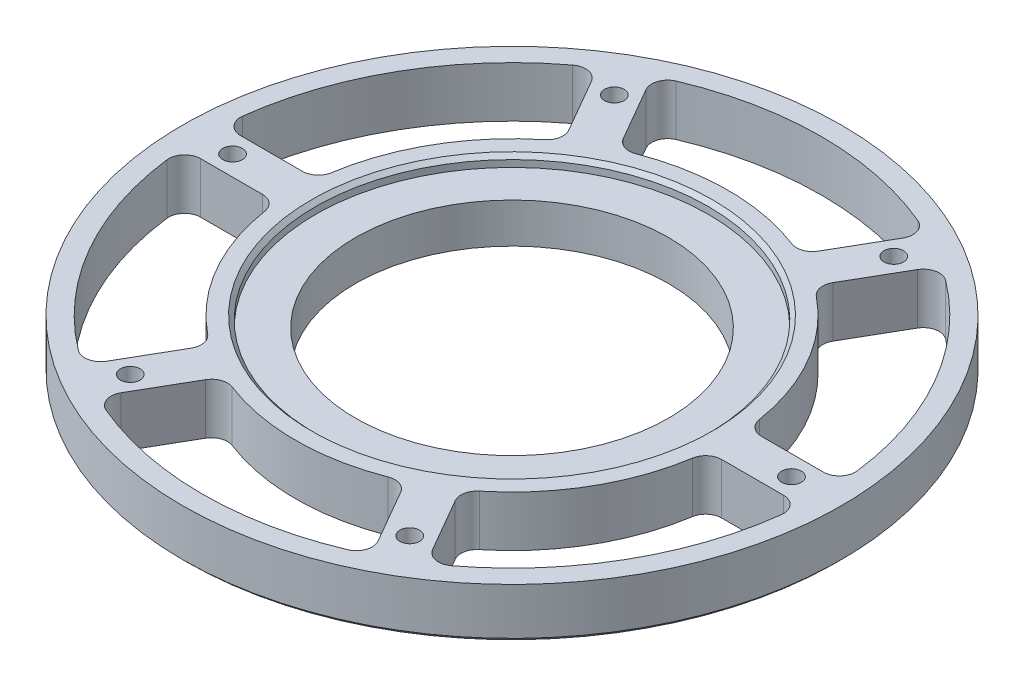
SolidWorks part; units mm, degrees
material "6061-T6 (SS)"
ref_plane "Front Plane" through (0, 0, 0) normal (0, 0, 1) x (1, 0, 0)
ref_plane "Top Plane" through (0, 0, 0) normal (0, 1, 0) x (1, 0, 0)
ref_plane "Right Plane" through (0, 0, 0) normal (1, 0, 0) x (0, 0, -1)
sketch "Sketch2" plane through (0, 0, 0) normal (1, 0, 0) x (0, 0, -1)
  line L0 (-39.2125, 0) -> (-82.55, 0)
  line L1 (-82.55, 0) -> (-82.55, 12.7)
  line L2 (-82.55, 12.7) -> (-49.2125, 12.7)
  line L3 (-49.2125, 12.7) -> (-49.2125, 10)
  line L4 (-49.2125, 10) -> (-39.2125, 10)
  line L5 (-39.2125, 10) -> (-39.2125, 0)
  dimension "D1" = 82.55
  dimension "D2" = 12.7
  dimension "D4" = 49.2125
  dimension "D5" = 10
  dimension "D3" = 10
ref_axis "Axis1" through (0, -0.635, 0) along (0, 1, 0)
revolve "Revolve1" add sketch "Sketch2" angle 360 about axis through (0, -0.635, 0) along (0, 1, 0)
hole_wizard "#10 (0.1935) Diameter Hole1" positions "Sketch6" profile "Sketch7" hole size "#10" standard "ANSI Inch" end condition through all
sketch "Sketch6" plane through (0, 12.7, 0) normal (0, 1, 0) x (1, 0, 0)
  line L0 (0, 0) -> (-69.8201, 120.932) construction
  line L2 (0, 0) -> (0, 109.0908) construction
  point P0 (-35, 60.6218)
  dimension "D1" = 30
  dimension "D2" = 70
sketch "Sketch7" plane through (-35, 12.7, -60.6218) normal (1, 0, 0) x (0, 0, 1)
  line L0 (0, 0) -> (0, 12.7)
  line L1 (0, 12.7) -> (2.4574, 12.7)
  line L2 (2.4574, 12.7) -> (2.4574, 0)
  line L5 (2.4574, 0) -> (0, 0)
  line L11 (0, -6.35) -> (0, 107.95) construction
  dimension "Thru Hole Dia." = 4.9149
  dimension "Thru Hole Depth" = 12.7
pattern_circular "CirPattern3" count 6 over 360 about axis through (0, -0.635, 0) along (0, 1, 0) of "#10 (0.1935) Diameter Hole1"
sketch "Sketch8" plane through (0, 12.7, 0) normal (0, 1, 0) x (1, 0, 0)
  line L0 (-34.3642, 69.5205) -> (-22.6606, 49.2493)
  line L1 (34.3642, 69.5205) -> (22.6606, 49.2493)
  line L2 (0, 0) -> (-35, 60.6218) construction
  line L4 (0, 0) -> (0, 93.9995) construction
  arc A0 (-22.6606, 49.2493) -> (22.6606, 49.2493) centre (0, 0) cw
  arc A1 (-34.3642, 69.5205) -> (34.3642, 69.5205) centre (0, 0) cw
  circle A2 centre (0, 0) radius 49.2125 construction
  circle A3 centre (0, 0) radius 82.55 construction
  dimension "D1" = 5
  dimension "D2" = 5
  dimension "D3" = 5
extrude "Cut-Extrude1" cut sketch "Sketch8" against normal through all
fillet "Fillet1" radius 4 4 edges at (34.3642, 6.35, -69.5205) (22.6606, 6.35, -49.2493) (-34.3642, 6.35, -69.5205) (-22.6606, 6.35, -49.2493)
pattern_circular "CirPattern4" count 6 over 360 about axis through (0, -0.635, 0) along (0, 1, 0) of "Cut-Extrude1", "Fillet1"
chamfer "Chamfer1" distance 1 angle 45 1 edges at (0, 12.7, -49.2125)
chamfer "Chamfer2" distance 1 angle 45 1 edges at (0, 0, -82.55)
equation "\"TubeDiameter\" = 6.500in"
equation "\"D1@Sketch2\"=\"TubeDiameter\"/2"
